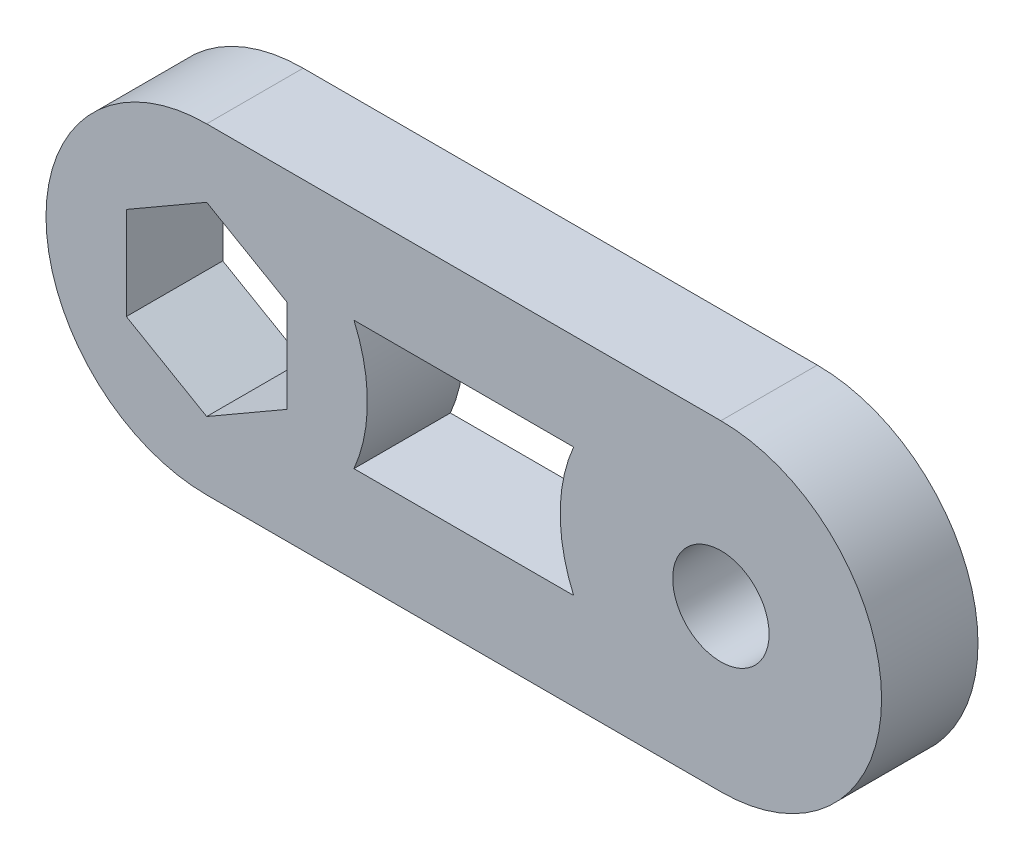
SolidWorks part; units mm, degrees
material "Plain Carbon Steel"
ref_plane "Front Plane" through (0, 0, 0) normal (0, 0, 1) x (1, 0, 0)
ref_plane "Top Plane" through (0, 0, 0) normal (0, 1, 0) x (1, 0, 0)
ref_plane "Right Plane" through (0, 0, 0) normal (1, 0, 0) x (0, 0, -1)
sketch "Sketch1" plane through (0, 0, 0) normal (0, 0, 1) x (1, 0, 0)
  line L0 (0, 0) -> (16, 0)
  line L1 (0, -5) -> (16, -5)
  line L2 (0, 5) -> (16, 5)
  circle A0 centre (16, 0) radius 1.5
  circle A1 centre (0, 0) radius 1.5
  arc A2 (0, -5) -> (0, 5) centre (0, 0) cw
  arc A3 (16, -5) -> (16, 5) centre (16, 0) ccw
  dimension "D2" = 3
  dimension "D1" = 3
extrude "Extrude1" add sketch "Sketch1" along normal blind 3 contours L1 A3 L2 A2 A1 A0 region at (-4.7214, 0, 0)
sketch "Sketch2" plane through (0, 0, 3) normal (0, 0, 1) x (1, 0, 0)
  line L1 (0, 2.8868) -> (-2.5, 1.4434)
  line L2 (-2.5, 1.4434) -> (-2.5, -1.4434)
  line L3 (-2.5, -1.4434) -> (0, -2.8868)
  line L4 (0, -2) -> (16, -2)
  line L5 (16, 2) -> (0, 2)
  line L6 (4.5826, -2) -> (11.4174, -2)
  line L7 (11.4174, 2) -> (4.5826, 2)
  line L8 (0, -2.8868) -> (2.5, -1.4434)
  line L9 (2.5, -1.4434) -> (2.5, 1.4434)
  line L10 (2.5, 1.4434) -> (0, 2.8868)
  circle A0 centre (16, 0) radius 1.5
  circle A1 centre (0, 0) radius 2.5 construction
  arc A2 (4.5826, -2) -> (4.5826, 2) centre (0, 0) ccw
  arc A3 (11.4174, 2) -> (11.4174, -2) centre (16, 0) ccw
  arc A4 (16, -2) -> (16, 2) centre (16, 0) ccw
  arc A5 (0, 2) -> (0, -2) centre (0, 0) ccw
  dimension "D2" = 3
  dimension "D3" = 5
  dimension "D1" = 3
extrude "Cut-Extrude1" cut sketch "Sketch2" against normal blind 10
move or copy body "Body-Move/Copy1" [suppressed] bodies to move or copy 103
move or copy body "Body-Move/Copy2" [suppressed] bodies to move or copy 103
move or copy body "Body-Move/Copy3" [suppressed] bodies to move or copy 103
